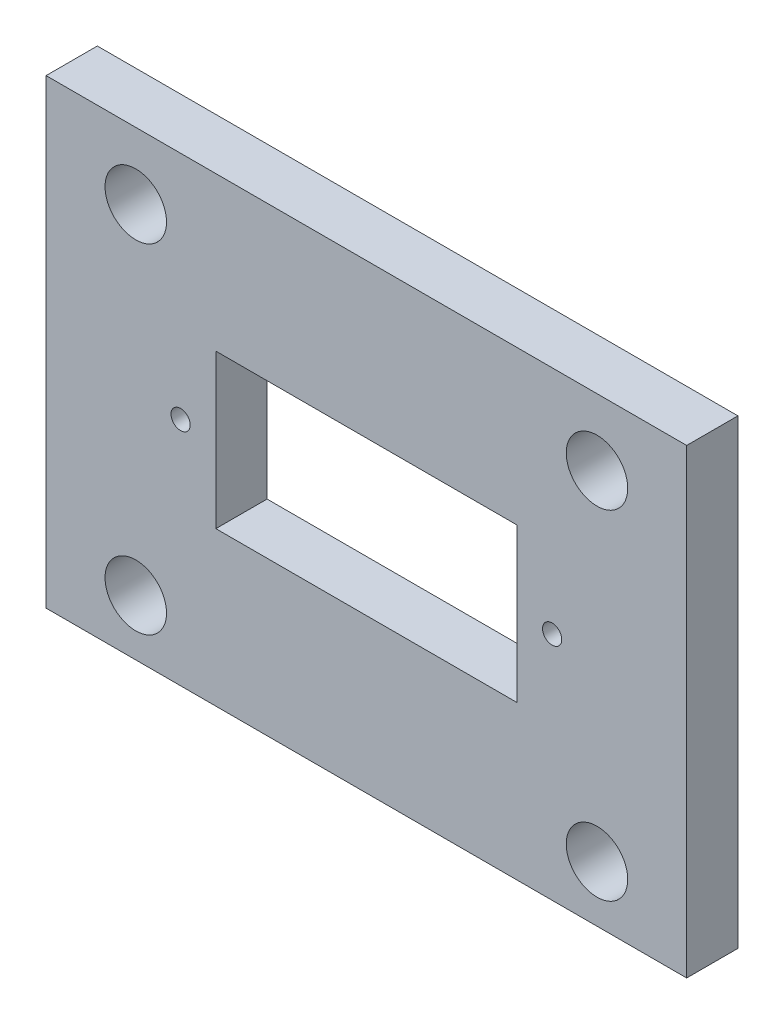
SolidWorks part; units mm, degrees
ref_plane "Front Plane" through (0, 0, 0) normal (0, 0, 1) x (1, 0, 0)
ref_plane "Top Plane" through (0, 0, 0) normal (0, 1, 0) x (1, 0, 0)
ref_plane "Right Plane" through (0, 0, 0) normal (1, 0, 0) x (0, 0, -1)
sketch "Sketch1" plane through (0, 0, 0) normal (0, 0, 1) x (1, 0, 0)
  line L0 (-33, 6) -> (0, 6) construction
  line L1 (0, 0) -> (-33, 0) construction
  line L2 (0, 0) -> (0, 12) construction
  line L3 (0, 12) -> (-33, 12) construction
  line L4 (-33, 0) -> (-33, 12) construction
  line L5 (-16.5, 12) -> (-16.5, 0)
  line L6 (-28.25, 12) -> (-4.75, 12)
  line L7 (-28.25, 12) -> (-28.25, 0)
  line L8 (-28.25, 0) -> (-4.75, 0)
  line L9 (-4.75, 12) -> (-4.75, 0)
  line L10 (-41.5, 24) -> (8.5, 24)
  line L11 (-41.5, 24) -> (-41.5, -12)
  line L12 (-41.5, -12) -> (8.5, -12)
  line L13 (8.5, 24) -> (8.5, -12)
  line L14 (-34.5, 18.7967) -> (-34.5, -7.6364) construction
  line L15 (1.5, 18.7967) -> (1.5, -7.6364) construction
  circle A0 centre (-31, 6) radius 0.65 construction
  circle A1 centre (-2, 6) radius 0.65 construction
  circle A2 centre (-34.5, 18.7967) radius 2.4
  circle A3 centre (-34.5, -7.6364) radius 2.4
  circle A4 centre (1.5, -7.6364) radius 2.4
  circle A5 centre (1.5, 18.7967) radius 2.4
  point P23 (0, 0)
  dimension "D5" = 1.3
  dimension "D12" = 4.8
  dimension "D1" = 33
  dimension "D2" = 12
  dimension "D3" = 29
  dimension "D4" = 2
  dimension "D6" = 23.5
  dimension "D7" = 4.75
  dimension "D8" = 36
  dimension "D9" = 18
  dimension "D10" = 50
  dimension "D11" = 25
  dimension "D13" = 36
  dimension "D14" = 7
extrude "Boss-Extrude1" add sketch "Sketch1" along normal blind 4 contours L7 L8 L5 L6 | L9 L6 L5 L8 | L10 L13 L12 L11 | A2 | A5 | A4 | A3 region at (-10.625, 6, 0) region at (-22.375, 6, 0)
sketch "Sketch2" plane through (0, 0, 4) normal (0, 0, 1) x (1, 0, 0)
  line L0 (-28.25, 12) -> (-28.25, 0) construction
  line L1 (-4.75, 12) -> (-4.75, 0) construction
  line L2 (-28.25, 12) -> (-4.75, 12) construction
  circle A0 centre (-31, 6) radius 0.75
  circle A1 centre (-2, 6) radius 0.75
  point P10 (0, 0)
  point P11 (0, 0)
  dimension "D1" = 1.5
  dimension "D2" = 2.75
  dimension "D3" = 2.75
  dimension "D4" = 6
extrude "Cut-Extrude1" cut sketch "Sketch2" against normal up to next
